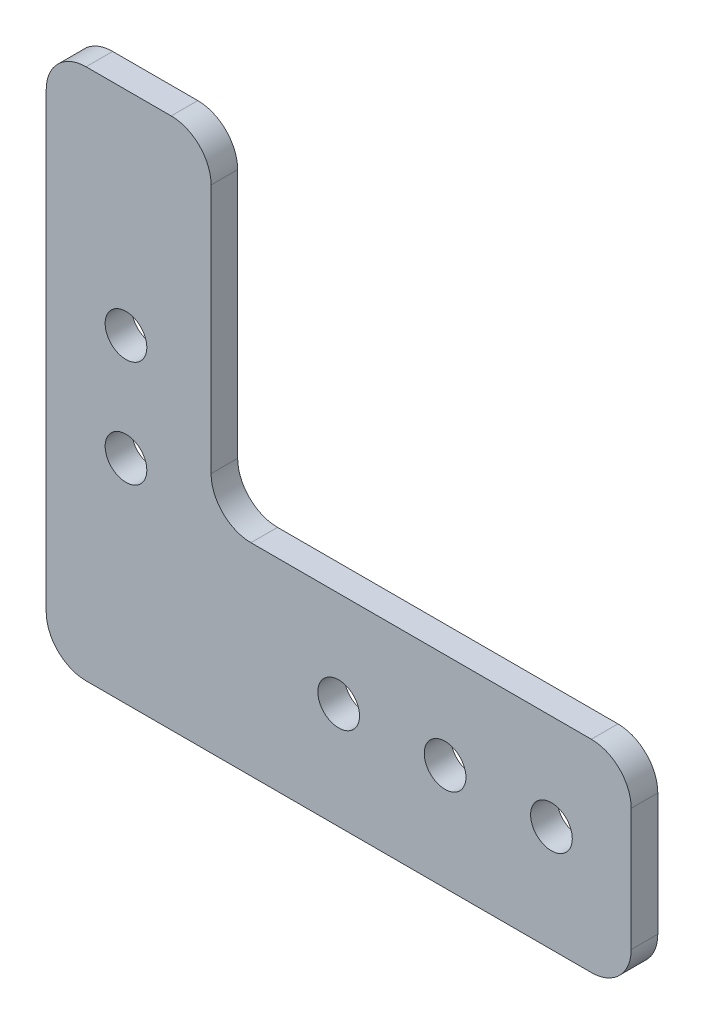
SolidWorks part; units mm, degrees
material "6061-T6 (SS)"
ref_plane "Front Plane" through (0, 0, 0) normal (0, 0, 1) x (1, 0, 0)
ref_plane "Top Plane" through (0, 0, 0) normal (0, 1, 0) x (1, 0, 0)
ref_plane "Right Plane" through (0, 0, 0) normal (1, 0, 0) x (0, 0, -1)
sketch "Sketch1" plane through (0, 0, 0) normal (0, 0, 1) x (1, 0, 0)
  line L0 (-10.795, 31.75) -> (-34.925, 31.75) construction
  line L1 (-34.925, -31.75) -> (34.925, -31.75)
  line L2 (-34.925, -31.75) -> (-34.925, 31.75)
  line L3 (-34.925, 31.75) -> (34.925, 31.75)
  line L4 (34.925, -31.75) -> (34.925, 31.75)
  line L5 (-34.925, -31.75) -> (34.925, 31.75) construction
  line L6 (-34.925, 31.75) -> (34.925, -31.75) construction
  line L7 (34.925, 31.75) -> (-10.795, 31.75)
  line L8 (34.925, 31.75) -> (34.925, -7.62)
  line L9 (34.925, -7.62) -> (-10.795, -7.62)
  line L10 (-10.795, 31.75) -> (-10.795, -7.62)
  line L19 (-25.4, 31.75) -> (-25.4, -31.75) construction
  circle A0 centre (-25.4, -19.05) radius 2.4892
  circle A1 centre (-25.4, -6.35) radius 2.4892
  circle A2 centre (-25.4, 6.35) radius 2.4892
  circle A4 centre (0, -19.05) radius 2.4892
  circle A5 centre (12.7, -19.05) radius 2.4892
  circle A6 centre (25.4, -19.05) radius 2.4892
  point P0 (0, 0)
  point P11 (0, 0)
  point P26 (0, 0)
  dimension "D7" = 4.9784
  dimension "D1" = 69.85
  dimension "D2" = 63.5
  dimension "D3" = 24.13
  dimension "D4" = 24.13
  dimension "D5" = 9.525
  dimension "D6" = 34.925
  dimension "D9" = 12.7
  dimension "D10" = 12.7
  dimension "D11" = 12.7
  dimension "D13" = 12.7
  dimension "D15" = 12.7
extrude "Boss-Extrude1" add sketch "Sketch1" along normal blind 3.175 contours L4 L9 L10 L3 A6 A5 A4 A2 A1 A0 | A0 region at (-8.3279, -8.0334, 0) region at (-25.4, -19.05, 0)
sketch "Sketch2" plane through (0, 0, 3.175) normal (0, 0, 1) x (1, 0, 0)
  line L1 (-10.795, 31.75) -> (-15.24, 31.75)
  line L2 (-10.795, 31.75) -> (-10.795, -7.62)
  line L3 (-10.795, -7.62) -> (-15.24, -7.62)
  line L4 (-15.24, 31.75) -> (-15.24, -7.62)
  point P5 (0, 0)
  dimension "D1" = 4.445
extrude "Cut-Extrude1" cut sketch "Sketch2" against normal through all
fillet "Fillet1" radius 4.7625 6 edges at (34.925, -7.62, 1.5875) (34.925, -31.75, 1.5875) (-34.925, 31.75, 1.5875) (-15.24, 31.75, 1.5875) (-15.24, -7.62, 1.5875) (-34.925, -31.75, 1.5875)
